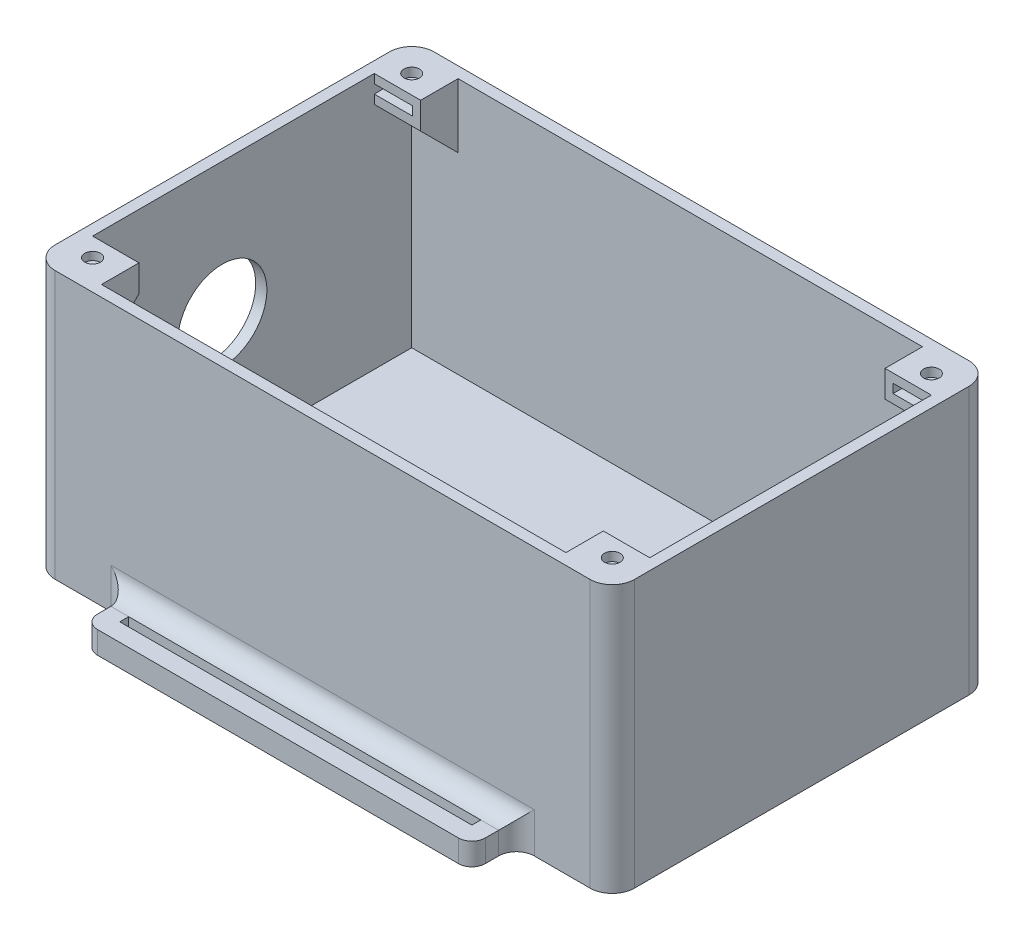
SolidWorks part; units mm, degrees
ref_plane "Piano frontale" through (0, 0, 0) normal (0, 0, 1) x (1, 0, 0)
ref_plane "Piano superiore" through (0, 0, 0) normal (0, 1, 0) x (1, 0, 0)
ref_plane "Piano destro" through (0, 0, 0) normal (1, 0, 0) x (0, 0, -1)
sketch "Schizzo1" plane through (0, 0, 0) normal (0, 1, 0) x (1, 0, 0)
  line L1 (0, 0) -> (130, 0)
  line L2 (0, 0) -> (0, 85)
  line L3 (0, 85) -> (130, 85)
  line L4 (130, 0) -> (130, 85)
  dimension "D1" = 130
  dimension "D2" = 85
extrude "Estrusione-Estrusione1" add sketch "Schizzo1" along normal blind 60
sketch "Schizzo3" plane through (0, 60, 0) normal (0, 1, 0) x (1, 0, 0)
  line L0 (130, 0) -> (130, 85) construction
  line L1 (2.5, 2.5) -> (127.5, 2.5)
  line L2 (2.5, 2.5) -> (2.5, 82.5)
  line L3 (2.5, 82.5) -> (127.5, 82.5)
  line L4 (127.5, 2.5) -> (127.5, 82.5)
  line L5 (130, 85) -> (0, 85) construction
  line L6 (0, 85) -> (0, 0) construction
  line L7 (0, 0) -> (130, 0) construction
  dimension "D1" = 2.5
  dimension "D2" = 2.5
  dimension "D3" = 2.5
  dimension "D4" = 2.5
extrude "Taglio-Estrusione1" cut sketch "Schizzo3" against normal blind 57.5
sketch "Schizzo4" plane through (0, 0, 0) normal (-1, 0, 0) x (0, 0, 1)
  line L0 (0, 60) -> (0, 0) construction
  line L5 (0, 0) -> (-85, 0) construction
  circle A0 centre (-40, 30) radius 10
  dimension "D1" = 20
  dimension "D2" = 40
  dimension "D3" = 30
extrude "Taglio-Estrusione2" cut sketch "Schizzo4" against normal blind 47.5
sketch "Schizzo5" plane through (0, 0, 0) normal (0, -1, 0) x (1, 0, 0)
  line L0 (0, 0) -> (130, 0) construction
  line L1 (95, -17) -> (120, -17)
  line L2 (95, -17) -> (95, -6)
  line L3 (95, -6) -> (120, -6)
  line L4 (120, -17) -> (120, -6)
  line L5 (130, 0) -> (130, -85) construction
  dimension "D1" = 11
  dimension "D2" = 25
  dimension "D3" = 6
  dimension "D4" = 10
fillet "Raccordo1" radius 5 1 edges at (0, 30, 0)
fillet "Raccordo2" radius 5 1 edges at (0, 30, -85)
fillet "Raccordo3" radius 5 1 edges at (130, 30, -85)
fillet "Raccordo4" radius 5 1 edges at (130, 30, 0)
sketch "Schizzo13" plane through (0, 2.5, 0) normal (0, 1, 0) x (1, 0, 0)
  line L0 (127.5, 82.5) -> (2.5, 82.5) construction
  line L2 (2.5, 82.5) -> (2.5, 2.5) construction
  line L7 (127.5, 2.5) -> (127.5, 82.5) construction
  line L8 (81.7, 36.7) -> (71.3, 36.7)
  line L9 (81.7, 36.7) -> (81.7, 28.3)
  line L10 (81.7, 28.3) -> (71.3, 28.3)
  line L11 (71.3, 36.7) -> (71.3, 28.3)
  line L12 (26.7, 36.7) -> (16.3, 36.7)
  line L13 (26.7, 36.7) -> (26.7, 28.3)
  line L14 (26.7, 28.3) -> (16.3, 28.3)
  line L15 (16.3, 36.7) -> (16.3, 28.3)
  circle A0 centre (20.5, 32.5) radius 1.75
  circle A1 centre (77.5, 32.5) radius 1.75
  dimension "D1" = 3.5
  dimension "D8" = 3.5
  dimension "D2" = 50
  dimension "D3" = 50
  dimension "D4" = 50
  dimension "D5" = 4.2
  dimension "D6" = 4.2
  dimension "D7" = 18
  dimension "D9" = 8.4
  dimension "D10" = 10.4
  dimension "D11" = 4.2
  dimension "D12" = 4.2
  dimension "D13" = 8.4
  dimension "D14" = 10.4
sketch "Schizzo14" plane through (0, 0, 0) normal (0, 0, 1) x (1, 0, 0)
  line L0 (5, 0) -> (125, 0) construction
  line L1 (21.5, 5) -> (108.5, 5)
  line L2 (21.5, 5) -> (21.5, 0)
  line L3 (21.5, 0) -> (108.5, 0)
  line L4 (108.5, 5) -> (108.5, 0)
  line L5 (5, 60) -> (5, 0) construction
  line L6 (125, 0) -> (125, 60) construction
  point P8 (21.5, 2.5)
  dimension "D1" = 0
  dimension "D2" = 5
  dimension "D3" = 16.5
  dimension "D4" = 16.5
extrude "Estrusione-Estrusione7" add sketch "Schizzo14" along normal blind 10
sketch "Schizzo15" plane through (0, 0, -85) normal (0, 0, -1) x (-1, 0, 0)
  line L0 (-125, 0) -> (-5, 0) construction
  line L1 (-108.5, 5) -> (-21.5, 5)
  line L2 (-108.5, 5) -> (-108.5, 0)
  line L3 (-108.5, 0) -> (-21.5, 0)
  line L4 (-21.5, 5) -> (-21.5, 0)
  line L5 (-125, 60) -> (-125, 0) construction
  line L6 (-5, 0) -> (-5, 60) construction
  point P8 (-108.5, 2.5)
  dimension "D1" = 0
  dimension "D2" = 5
  dimension "D3" = 16.5
  dimension "D4" = 16.5
extrude "Estrusione-Estrusione8" add sketch "Schizzo15" along normal blind 10
sketch "Schizzo16" plane through (0, 5, 0) normal (0, 1, 0) x (1, 0, 0)
  line L0 (108.5, -10) -> (21.5, -10) construction
  line L1 (25.5, -4) -> (104.5, -4)
  line L2 (25.5, -4) -> (25.5, -6)
  line L3 (25.5, -6) -> (104.5, -6)
  line L4 (104.5, -4) -> (104.5, -6)
  line L5 (108.5, 0) -> (21.5, 0) construction
  line L6 (21.5, -10) -> (21.5, 0) construction
  line L7 (108.5, -10) -> (108.5, 0) construction
  dimension "D1" = 4
  dimension "D2" = 4
  dimension "D3" = 4
  dimension "D4" = 4
extrude "Taglio-Estrusione4" cut sketch "Schizzo16" against normal through all and the other way through all
sketch "Schizzo17" plane through (0, 5, 0) normal (0, 1, 0) x (1, 0, 0)
  line L0 (21.5, 95) -> (108.5, 95) construction
  line L1 (25.5, 91) -> (104.5, 91)
  line L2 (25.5, 91) -> (25.5, 89)
  line L3 (25.5, 89) -> (104.5, 89)
  line L4 (104.5, 91) -> (104.5, 89)
  line L5 (125, 85) -> (5, 85) construction
  line L6 (21.5, 95) -> (21.5, 85) construction
  line L7 (108.5, 95) -> (108.5, 85) construction
  dimension "D1" = 4
  dimension "D2" = 4
  dimension "D3" = 4
  dimension "D4" = 4
extrude "Taglio-Estrusione5" cut sketch "Schizzo17" against normal through all both and the other way through all
fillet "Raccordo10" radius 3 2 edges at (21.5, 2.5, 10) (108.5, 2.5, 10)
fillet "Raccordo11" radius 4 3 edges at (108.5, 2.5, 0) (65, 5, 0) (21.5, 2.5, 0)
sketch "Schizzo18" plane through (0, 60, 0) normal (0, 1, 0) x (1, 0, 0)
  line L0 (2.5, 82.5) -> (2.5, 2.5) construction
  line L1 (2.5, 10.9) -> (12.9, 10.9)
  line L2 (2.5, 10.9) -> (2.5, 2.5)
  line L3 (2.5, 2.5) -> (12.9, 2.5)
  line L4 (12.9, 10.9) -> (12.9, 2.5)
  line L5 (2.5, 2.5) -> (127.5, 2.5) construction
  line L6 (10.9, 10.9) -> (10.9, 2.5) construction
  circle A0 centre (6.7, 6.7) radius 1.75
  dimension "D6" = 3.5
  dimension "D1" = 8.4
  dimension "D2" = 10.4
  dimension "D3" = 2
  dimension "D4" = 4.2
  dimension "D5" = 4.2
extrude "Estrusione-Estrusione9" add sketch "Schizzo18" against normal blind 6
sketch "Schizzo19" plane through (0, 0, -10.9) normal (0, 0, -1) x (-1, 0, 0)
  line L0 (-2.5, 54) -> (-2.5, 60) construction
  line L1 (-2.5, 58) -> (-11.1, 58)
  line L2 (-2.5, 58) -> (-2.5, 56)
  line L3 (-2.5, 56) -> (-11.1, 56)
  line L4 (-11.1, 58) -> (-11.1, 56)
  line L5 (-12.9, 60) -> (-2.5, 60) construction
  dimension "D1" = 2
  dimension "D2" = 2
  dimension "D3" = 8.6
extrude "Taglio-Estrusione6" cut sketch "Schizzo19" against normal up to surface (8.4 mm away) up to face at (47.6333, 38.8333, -2.5)
chamfer "Smusso1" distance 8.4 angle 45 1 edges at (7.7, 54, -2.5)
sketch "Schizzo20" plane through (0, 58, 0) normal (0, -1, 0) x (1, 0, 0)
  circle A0 centre (6.7, -6.7) radius 1.75
  circle A1 centre (6.7, -6.7) radius 1.75 construction
extrude "Estrusione-Estrusione11" add sketch "Schizzo20" against normal blind 0.2
fillet "Raccordo12" radius 4 3 edges at (21.5, 2.5, -85) (65, 5, -85) (108.5, 2.5, -85)
sketch "Schizzo23" plane through (0, 60, 0) normal (0, 1, 0) x (1, 0, 0)
  line L0 (2.5, 82.5) -> (2.5, 10.9) construction
  line L1 (2.5, 74.1) -> (12.9, 74.1)
  line L2 (2.5, 74.1) -> (2.5, 82.5)
  line L3 (2.5, 82.5) -> (12.9, 82.5)
  line L4 (12.9, 74.1) -> (12.9, 82.5)
  line L5 (127.5, 82.5) -> (2.5, 82.5) construction
  circle A0 centre (6.7, 78.3) radius 1.75
  dimension "D3" = 3.5
  dimension "D1" = 8.4
  dimension "D2" = 10.4
  dimension "D4" = 4.2
  dimension "D5" = 4.2
extrude "Estrusione-Estrusione12" add sketch "Schizzo23" against normal blind 6
sketch "Schizzo24" plane through (0, 0, -74.1) normal (0, 0, 1) x (1, 0, 0)
  line L0 (2.5, 54) -> (2.5, 60) construction
  line L1 (2.5, 58) -> (11.1, 58)
  line L2 (2.5, 58) -> (2.5, 56)
  line L3 (2.5, 56) -> (11.1, 56)
  line L4 (11.1, 58) -> (11.1, 56)
  line L5 (2.5, 60) -> (12.9, 60) construction
  dimension "D1" = 8.6
  dimension "D2" = 2
  dimension "D3" = 2
extrude "Taglio-Estrusione7" cut sketch "Schizzo24" against normal up to surface (8.4 mm away) up to face at (47.6333, 38.8333, -82.5)
chamfer "Smusso2" distance 8.4 angle 45 1 edges at (7.7, 54, -82.5)
sketch "Schizzo26" plane through (0, 60, 0) normal (0, 1, 0) x (1, 0, 0)
  line L0 (127.5, 2.5) -> (127.5, 82.5) construction
  line L1 (127.5, 74.1) -> (117.1, 74.1)
  line L2 (127.5, 74.1) -> (127.5, 82.5)
  line L3 (127.5, 82.5) -> (117.1, 82.5)
  line L4 (117.1, 74.1) -> (117.1, 82.5)
  line L5 (127.5, 82.5) -> (12.9, 82.5) construction
  circle A0 centre (123.3, 78.3) radius 1.75
  dimension "D3" = 3.5
  dimension "D1" = 8.4
  dimension "D2" = 10.4
  dimension "D4" = 4.2
  dimension "D5" = 4.2
extrude "Estrusione-Estrusione13" add sketch "Schizzo26" against normal blind 6
sketch "Schizzo27" plane through (0, 0, -74.1) normal (0, 0, 1) x (1, 0, 0)
  line L0 (127.5, 54) -> (127.5, 60) construction
  line L1 (118.9, 58) -> (127.5, 58)
  line L2 (118.9, 58) -> (118.9, 56)
  line L3 (118.9, 56) -> (127.5, 56)
  line L4 (127.5, 58) -> (127.5, 56)
  line L5 (117.1, 60) -> (127.5, 60) construction
  dimension "D1" = 2
  dimension "D2" = 2
  dimension "D3" = 8.6
extrude "Taglio-Estrusione8" cut sketch "Schizzo27" against normal up to surface (8.4 mm away) up to face at (65, 40.525, -82.5)
chamfer "Smusso3" distance 8.4 angle 45 1 edges at (122.3, 54, -82.5)
sketch "Schizzo28" plane through (0, 60, 0) normal (0, 1, 0) x (1, 0, 0)
  line L0 (12.9, 2.5) -> (127.5, 2.5) construction
  line L1 (117.1, 2.5) -> (127.5, 2.5)
  line L2 (117.1, 2.5) -> (117.1, 10.9)
  line L3 (117.1, 10.9) -> (127.5, 10.9)
  line L4 (127.5, 2.5) -> (127.5, 10.9)
  line L5 (127.5, 2.5) -> (127.5, 74.1) construction
  circle A0 centre (123.3, 6.7) radius 1.75
  point P10 (122.3, 2.5)
  dimension "D3" = 3.5
  dimension "D1" = 8.4
  dimension "D2" = 10.4
  dimension "D4" = 4.2
  dimension "D5" = 4.2
extrude "Estrusione-Estrusione14" add sketch "Schizzo28" against normal blind 6
sketch "Schizzo29" plane through (117.1, 0, 0) normal (-1, 0, 0) x (0, 0, 1)
  line L0 (-2.5, 54) -> (-2.5, 60) construction
  line L1 (-2.5, 56) -> (-11.1, 56)
  line L2 (-2.5, 56) -> (-2.5, 58)
  line L3 (-2.5, 58) -> (-11.1, 58)
  line L4 (-11.1, 56) -> (-11.1, 58)
  line L5 (-10.9, 60) -> (-2.5, 60) construction
  dimension "D1" = 2
  dimension "D2" = 2
  dimension "D3" = 8.6
sketch "Schizzo30" plane through (0, 0, -10.9) normal (0, 0, -1) x (-1, 0, 0)
  line L0 (-127.5, 54) -> (-127.5, 60) construction
  line L1 (-127.5, 58) -> (-118.9, 58)
  line L2 (-127.5, 58) -> (-127.5, 56)
  line L3 (-127.5, 56) -> (-118.9, 56)
  line L4 (-118.9, 58) -> (-118.9, 56)
  line L5 (-127.5, 60) -> (-117.1, 60) construction
  dimension "D1" = 2
  dimension "D2" = 2
  dimension "D3" = 8.6
extrude "Taglio-Estrusione10" cut sketch "Schizzo30" against normal up to surface (8.4 mm away) up to face at (65, 40.525, -2.5)
chamfer "Smusso5" distance 8.4 angle 45 1 edges at (122.3, 54, -2.5)
extrude "Estrusione-Estrusione15" add sketch "Schizzo13" along normal blind 6
sketch "Schizzo34" plane through (0, 0, -28.3) normal (0, 0, 1) x (1, 0, 0)
  line L0 (16.3, 8.5) -> (16.3, 2.5) construction
  line L1 (16.3, 6.5) -> (24.9, 6.5)
  line L2 (16.3, 6.5) -> (16.3, 4.5)
  line L3 (16.3, 4.5) -> (24.9, 4.5)
  line L4 (24.9, 6.5) -> (24.9, 4.5)
  line L5 (81.7, 8.5) -> (81.7, 2.5) construction
  line L6 (81.7, 6.5) -> (73.1, 6.5)
  line L7 (81.7, 6.5) -> (81.7, 4.5)
  line L8 (81.7, 4.5) -> (73.1, 4.5)
  line L9 (73.1, 6.5) -> (73.1, 4.5)
  line L10 (16.3, 8.5) -> (26.7, 8.5) construction
  line L11 (71.3, 8.5) -> (81.7, 8.5) construction
  dimension "D1" = 2
  dimension "D2" = 2
  dimension "D3" = 8.6
  dimension "D4" = 2
  dimension "D5" = 2
  dimension "D6" = 8.6
extrude "Taglio-Estrusione11" cut sketch "Schizzo34" against normal up to surface (8.4 mm away) up to face at (21.5, 5.5, -36.7)
fillet "Raccordo13" radius 3 2 edges at (108.5, 2.5, -95) (21.5, 2.5, -95)
sketch "Schizzo35" plane through (0, 2.5, 0) normal (0, 1, 0) x (1, 0, 0)
  line L1 (81.7, 28.3) -> (83.7, 28.3)
  line L2 (81.7, 28.3) -> (81.7, 36.7)
  line L3 (81.7, 36.7) -> (83.7, 36.7)
  line L4 (83.7, 28.3) -> (83.7, 36.7)
  dimension "D1" = 2
  dimension "D2" = 8.4
extrude "Estrusione-Estrusione16" add sketch "Schizzo35" along normal up to surface (6 mm away) up to face at (76.5, 8.5, -32.5)
sketch "Schizzo36" plane through (0, 2.5, 0) normal (0, 1, 0) x (1, 0, 0)
  line L1 (16.3, 36.7) -> (14.3, 36.7)
  line L2 (16.3, 36.7) -> (16.3, 28.3)
  line L3 (16.3, 28.3) -> (14.3, 28.3)
  line L4 (14.3, 36.7) -> (14.3, 28.3)
  dimension "D1" = 2
  dimension "D2" = 8.4
extrude "Estrusione-Estrusione17" add sketch "Schizzo36" along normal up to surface (6 mm away) up to face at (21.5, 8.5, -32.5)
sketch "Schizzo37" plane through (0, 0, -85) normal (0, 0, -1) x (-1, 0, 0)
  line L0 (-125, 21.6314) -> (-5, 21.6314) construction
  line L1 (-125, 60) -> (-125, 0) construction
  line L2 (-5, 0) -> (-5, 60) construction
  text T0 "                 MILANO 1863" font "Arial" height 5
extrude "Taglio-Estrusione12" cut sketch "Schizzo37" against normal blind 1.5
sketch "Schizzo38" plane through (0, 0, -85) normal (0, 0, -1) x (-1, 0, 0)
  line L0 (-125, 30.3642) -> (-5, 30.3642) construction
  line L1 (-125, 60) -> (-125, 0) construction
  line L2 (-5, 0) -> (-5, 60) construction
  text T0 "         POLITECNICO " font "Arial" height 6.25
extrude "Taglio-Estrusione13" cut sketch "Schizzo38" against normal blind 1.5
